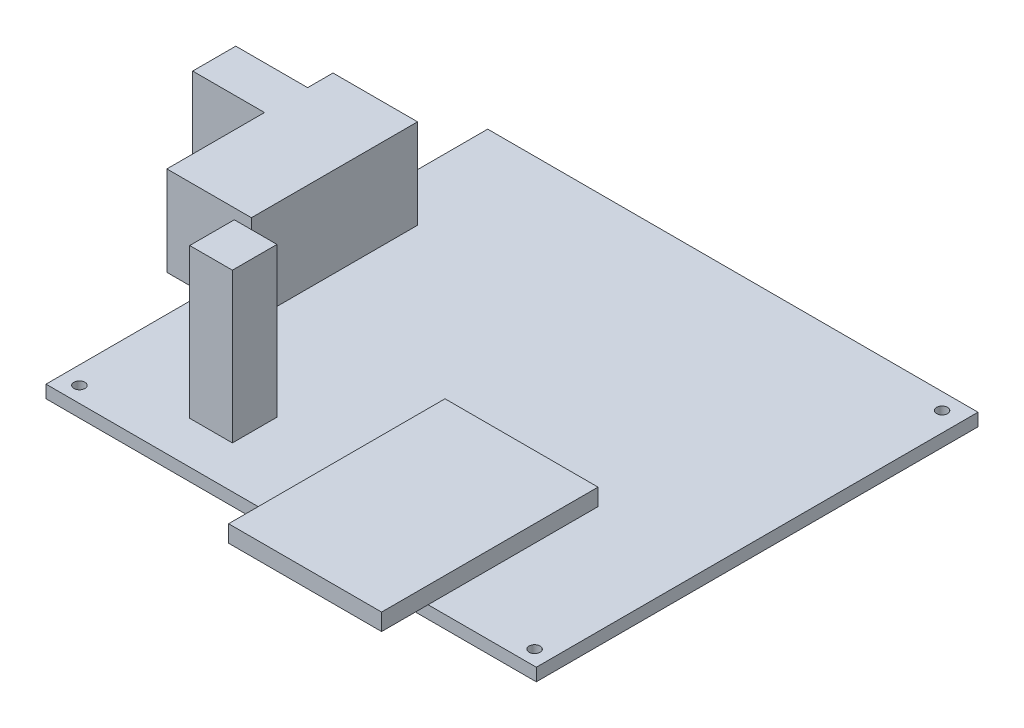
SolidWorks part; units mm, degrees
ref_plane "Front Plane" through (0, 0, 0) normal (0, 0, 1) x (1, 0, 0)
ref_plane "Top Plane" through (0, 0, 0) normal (0, 1, 0) x (1, 0, 0)
ref_plane "Right Plane" through (0, 0, 0) normal (1, 0, 0) x (0, 0, -1)
sketch "Sketch1" plane through (0, 0, 0) normal (0, 1, 0) x (1, 0, 0)
  line L0 (1.45, 1.85) -> (0, 1.85) construction
  line L1 (0, 0) -> (58, 0)
  line L2 (0, 0) -> (0, 52.25)
  line L3 (0, 52.25) -> (58, 52.25)
  line L4 (58, 0) -> (58, 52.25)
  line L5 (2.1, 1.2) -> (2.1, 0) construction
  line L6 (56.05, 1.1) -> (56.05, 0) construction
  line L7 (56.7, 1.75) -> (58, 1.75) construction
  line L8 (56.35, 50.3) -> (58, 50.3) construction
  line L9 (55.7, 50.95) -> (55.7, 52.25) construction
  line L10 (58, 26.125) -> (0, 26.125) construction
  line L11 (27.1, -5.5) -> (45.2, -5.5)
  line L12 (27.1, -5.5) -> (27.1, 20.1)
  line L13 (27.1, 20.1) -> (45.2, 20.1)
  line L14 (45.2, -5.5) -> (45.2, 20.1)
  line L15 (-4.3, 38.25) -> (5.7, 38.25)
  line L16 (-4.3, 38.25) -> (-4.3, 18.6)
  line L17 (-4.3, 18.6) -> (5.7, 18.6)
  line L18 (5.7, 38.25) -> (5.7, 18.6)
  line L19 (-4.3, 35.25) -> (-12.8, 35.25)
  line L20 (-4.3, 35.25) -> (-4.3, 30.15)
  line L21 (-4.3, 30.15) -> (-12.8, 30.15)
  line L22 (-12.8, 35.25) -> (-12.8, 30.15)
  line L23 (12, 10.276) -> (17.048, 10.276)
  line L24 (12, 10.276) -> (12, 5)
  line L25 (12, 5) -> (17.048, 5)
  line L26 (17.048, 10.276) -> (17.048, 5)
  line L27 (29, 52.25) -> (29, 0) construction
  circle A0 centre (2.1, 1.85) radius 0.65
  circle A1 centre (56.05, 1.75) radius 0.65
  circle A2 centre (55.7, 50.3) radius 0.65
  dimension "D1" = 1.3
  dimension "D2" = 1.45
  dimension "D3" = 1.2
  dimension "D4" = 1.1
  dimension "D5" = 1.3
  dimension "D6" = 1.65
  dimension "D7" = 1.3
  dimension "D8" = 58
  dimension "D9" = 52.25
  dimension "D10" = 19.65
  dimension "D11" = 12.8
  dimension "D12" = 25.6
  dimension "D13" = 18.1
  dimension "D14" = 5.5
  dimension "D15" = 8.5
  dimension "D16" = 5.7
  dimension "D17" = 5.1
  dimension "D18" = 18.5
  dimension "D19" = 3
  dimension "D20" = 14
  dimension "D21" = 5
  dimension "D22" = 12
extrude "Boss-Extrude1" add sketch "Sketch1" against normal blind 1.5 contours L15 L18 L17 L2 L1 L12 L13 L14 L4 L3 A2 A1 A0 | L1 L14 L13 L12 | L18 L15 L2 L17 | L26 L23 L24 L25 region at (29.2685, 0, -28.5479) region at (36.15, 0, -10.05) region at (2.85, 0, -28.425) region at (14.524, 0, -7.638)
extrude "Boss-Extrude2" add sketch "Sketch1<3>" along normal blind 10.6 contours L18 L15 L2 L17 | L16 L17 L2 L15 | L19 L22 L21 L16 region at (-2.15, 0, -28.425) region at (2.85, 0, -28.425) region at (-8.55, 0, -32.7)
sketch "Sketch1<3>" plane through (0, 0, 0) normal (0, 1, 0) x (1, 0, 0) same geometry as "Sketch1"
extrude "Boss-Extrude3" add sketch "Sketch1<4>" along normal blind 2 contours L1 L14 L13 L12 | L11 L14 L1 L12 region at (36.15, 0, -10.05) region at (36.15, 0, 2.75)
sketch "Sketch1<4>" plane through (0, 0, 0) normal (0, 1, 0) x (1, 0, 0) same geometry as "Sketch1"
extrude "Boss-Extrude4" add sketch "Sketch1<5>" against normal blind 3 and the other way blind 19.2 from surface contours L26 L23 L24 L25 region at (14.524, 0, -7.638) starting at face at (55.7, -1.5, -49.65)
sketch "Sketch1<5>" plane through (0, 0, 0) normal (0, 1, 0) x (1, 0, 0) same geometry as "Sketch1"
ref_point "Point1"
ref_axis "Axis1" through (29, 0, -26.125) along (0, 1, 0)
equation "\"D1@Boss-Extrude2\"=10.6"
equation "\"D1@Boss-Extrude4\"=6.5-.8"
equation "\"D2@Boss-Extrude4\"=1.5+17.7"
